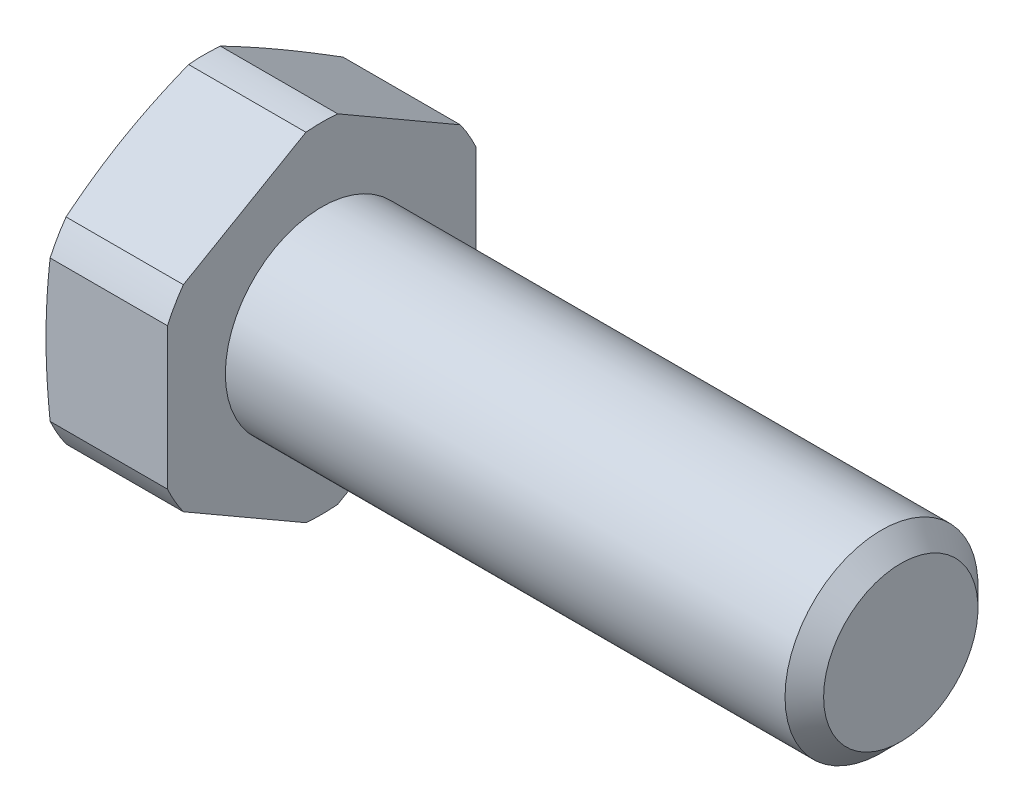
SolidWorks part; units mm, degrees
ref_plane "Спереди" through (0, 0, 0) normal (0, 0, 1) x (1, 0, 0)
ref_plane "Сверху" through (0, 0, 0) normal (0, 1, 0) x (1, 0, 0)
ref_plane "Справа" through (0, 0, 0) normal (1, 0, 0) x (0, 0, -1)
sketch "Эскиз1" plane through (0, 0, 0) normal (0, 0, 1) x (1, 0, 0)
  line L0 (-1000, 0) -> (49000, 0) construction
  line L1 (-6.4, 0) -> (-6.4, 7.6)
  line L2 (-6.4, 7.6) -> (-6.0785, 8.8)
  line L3 (-6.0785, 8.8) -> (0, 8.8)
  line L4 (0, 8.8) -> (0, 5)
  line L5 (0, 5) -> (29, 5)
  line L6 (30, 4) -> (30, 0)
  line L7 (30, 5) -> (30.75, 6.299) construction
  line L8 (30.75, 6.299) -> (31.5, 5) construction
  line L9 (31.5, 5) -> (30, 5) construction
  line L10 (30.75, 6.299) -> (30.75, 5) construction
  line L11 (30.75, 6.299) -> (0.75, 6.299) construction
  line L12 (29, 5) -> (30, 4)
  line L13 (30, 5) -> (29.5, 4.5) construction
  line L14 (-6.4, 7.6) -> (-22.4, 7.6) construction
  line L15 (-6.4, 0) -> (30, 0)
  dimension "D1" = 1
  dimension "D2" = 15
revolve "Повернуть1" add sketch "Эскиз1" angle 360 about L0
cosmetic thread "Условное изображение резьбы1" parameters "D1"=30, "D2"=7.4019
sketch "Эскиз2" plane through (-6.4, 0, 0) normal (-1, 0, 0) x (0, 0, 1)
  line L1 (0, 9.2376) -> (-8, 4.6188)
  line L2 (-8, 4.6188) -> (-8, -4.6188)
  line L3 (-8, -4.6188) -> (0, -9.2376)
  line L4 (0, -9.2376) -> (8, -4.6188)
  line L5 (8, -4.6188) -> (8, 4.6188)
  line L6 (8, 4.6188) -> (0, 9.2376)
  circle A0 centre (0, 0) radius 8 construction
  dimension "D1" = 16
extrude "Вырез-Вытянуть1" cut sketch "Эскиз2" against normal up to surface (36.4 mm away) flip side to cut up to face at (30, 0, 4)
other "PropertyManager"
equation "\"D1@Эскиз1\"=\"_d_@Эскиз1\"/10"
equation "\"D@Эскиз1\"=\"S_@Эскиз1\"*0.95"
equation "\"D1@Эскиз2\"=\"S_@Эскиз1\""
equation "\"D1@Условное изображение резьбы1\"=\"b_@Эскиз1\""
equation "\"D2@Условное изображение резьбы1\"=\"_d_@Эскиз1\"-\"dr@Эскиз1\"*2"
